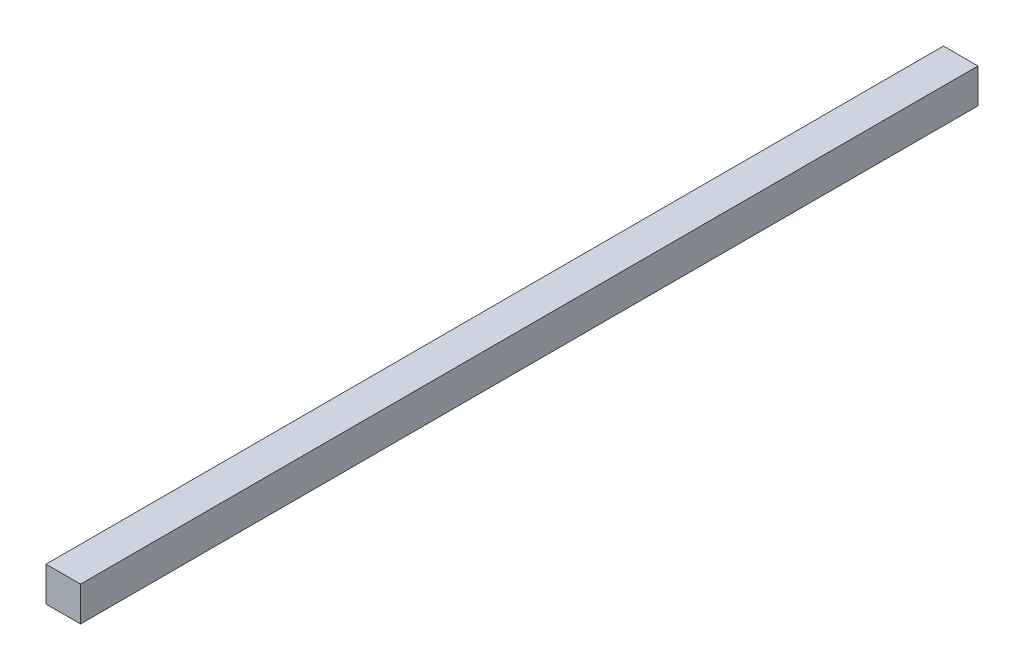
SolidWorks part; units mm, degrees
material "6061 Alloy"
ref_plane "Front Plane" through (0, 0, 0) normal (0, 0, 1) x (1, 0, 0)
ref_plane "Top Plane" through (0, 0, 0) normal (0, 1, 0) x (1, 0, 0)
ref_plane "Right Plane" through (0, 0, 0) normal (1, 0, 0) x (0, 0, -1)
sketch "Sketch1" plane through (0, 0, 0) normal (0, 0, 1) x (1, 0, 0)
  line L5 (-12.7, -12.7) -> (12.7, -12.7)
  line L6 (-12.7, -12.7) -> (-12.7, 12.7)
  line L7 (-12.7, 12.7) -> (12.7, 12.7)
  line L8 (12.7, -12.7) -> (12.7, 12.7)
  line L9 (-12.7, -12.7) -> (12.7, 12.7) construction
  line L10 (-12.7, 12.7) -> (12.7, -12.7) construction
  point P0 (0, 0)
  dimension "D1" = 25.4
  dimension "D2" = 25.4
extrude "Boss-Extrude1" add sketch "Sketch1" along normal blind 660.4
